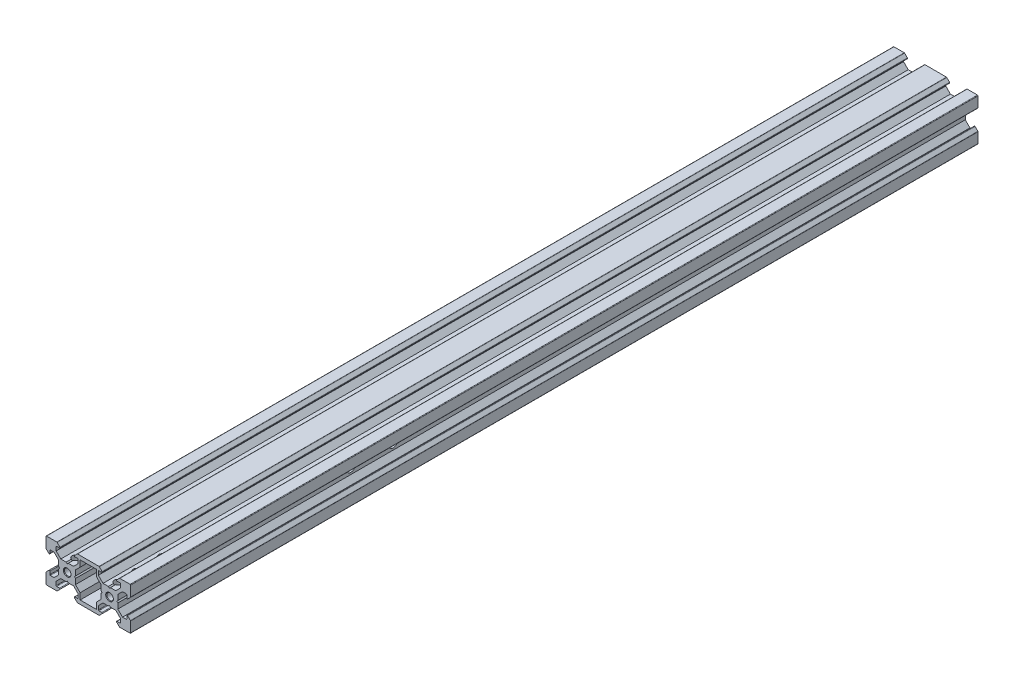
SolidWorks part; units mm, degrees
ref_plane "Alzado" through (0, 0, 0) normal (0, 0, 1) x (1, 0, 0)
ref_plane "Planta" through (0, 0, 0) normal (0, 1, 0) x (1, 0, 0)
ref_plane "Vista lateral" through (0, 0, 0) normal (1, 0, 0) x (0, 0, -1)
sketch "Croquis1" plane through (0, 0, 0) normal (0, 0, 1) x (1, 0, 0)
  line L0 (-10.0414, 10) -> (-10.0414, 8.2) construction
  line L1 (-13.8828, 8.2) -> (-6.2, 8.2)
  line L2 (-13.8828, -8.2) -> (-6.2, -8.2)
  line L4 (-4.8096, 9.9268) -> (-3.5096, 8.6268)
  line L5 (-3.6864, 8.2) -> (-5.0429, 8.2)
  line L6 (-5.2929, 7.95) -> (-5.2929, 6.2)
  line L13 (-14.8728, 8.2) -> (-16.6, 8.2)
  line L14 (-5.2929, 6.2) -> (-3.0929, 4)
  line L15 (-3.0929, 4) -> (-0.5828, 4)
  line L16 (-16.0828, 0.5) -> (-16.5828, 0)
  line L17 (-16.0828, 3.0101) -> (-16.0828, 0.5)
  line L18 (-13.8828, 5.2101) -> (-16.0828, 3.0101)
  line L19 (-13.8828, 8.2) -> (-13.8828, 5.2101)
  line L23 (-16.0828, -3.0101) -> (-16.0828, -0.5)
  line L24 (-16.0828, -0.5) -> (-16.5828, 0)
  line L25 (-13.8828, -5.2101) -> (-16.0828, -3.0101)
  line L26 (-13.8828, -8.2) -> (-13.8828, -5.2101)
  line L29 (-0.5828, 4) -> (-0.0828, 3.5)
  line L30 (-0.0828, 3.5) -> (0.4172, 4)
  line L31 (0.4172, 4) -> (2.9272, 4)
  line L32 (2.9272, 4) -> (5.1272, 6.2)
  line L33 (5.1272, 6.2) -> (5.1272, 7.95)
  line L34 (4.8772, 8.2) -> (3.5207, 8.2)
  line L35 (3.3439, 8.6268) -> (4.6439, 9.9268)
  line L36 (4.8207, 10) -> (9.6672, 10)
  line L37 (9.9172, 9.75) -> (9.9172, 4.9036)
  line L38 (9.8439, 4.7268) -> (8.5439, 3.4268)
  line L39 (8.1172, 3.6036) -> (8.1172, 4.9601)
  line L40 (7.8672, 5.2101) -> (6.1172, 5.2101)
  line L41 (6.1172, 5.2101) -> (3.9172, 3.0101)
  line L42 (3.9172, 3.0101) -> (3.9172, 0.5)
  line L43 (3.9172, 0.5) -> (3.4172, 0)
  line L44 (3.4172, 0) -> (3.9172, -0.5)
  line L45 (3.9172, -0.5) -> (3.9172, -3.0101)
  line L46 (3.9172, -3.0101) -> (6.1172, -5.2101)
  line L47 (6.1172, -5.2101) -> (7.8672, -5.2101)
  line L48 (8.1172, -4.9601) -> (8.1172, -3.6036)
  line L49 (8.5439, -3.4268) -> (9.8439, -4.7268)
  line L50 (9.9172, -4.9036) -> (9.9172, -9.75)
  line L51 (9.6672, -10) -> (4.8207, -10)
  line L52 (4.6439, -9.9268) -> (3.3439, -8.6268)
  line L53 (3.5207, -8.2) -> (4.8772, -8.2)
  line L54 (5.1272, -7.95) -> (5.1272, -6.2)
  line L55 (5.1272, -6.2) -> (2.9272, -4)
  line L56 (2.9272, -4) -> (0.4172, -4)
  line L57 (0.4172, -4) -> (-0.0828, -3.5)
  line L58 (-0.0828, -3.5) -> (-0.5828, -4)
  line L59 (-0.5828, -4) -> (-3.0929, -4)
  line L60 (-3.0929, -4) -> (-5.2929, -6.2)
  line L61 (-5.2929, -6.2) -> (-5.2929, -7.95)
  line L62 (-5.0429, -8.2) -> (-3.6864, -8.2)
  line L63 (-3.5096, -8.6268) -> (-4.8096, -9.9268)
  line L64 (-6.2, -8.2) -> (-6.2, -5.2101)
  line L65 (-6.2, -5.2101) -> (-4, -3.0101)
  line L66 (-4, -3.0101) -> (-4, -0.5)
  line L67 (-4, -0.5) -> (-3.5, 0)
  line L68 (-4, 0.5) -> (-3.5, 0)
  line L69 (-4, 3.0101) -> (-4, 0.5)
  line L70 (-6.2, 5.2101) -> (-4, 3.0101)
  line L71 (-6.2, 8.2) -> (-6.2, 5.2101)
  line L164 (-26.2, 5.2101) -> (-24, 3.0101)
  line L165 (-24, 3.0101) -> (-24, 0.5)
  line L166 (-24, 0.5) -> (-23.5, 0)
  line L167 (-23.5, 0) -> (-24, -0.5)
  line L168 (-24, -0.5) -> (-24, -3.0101)
  line L169 (-24, -3.0101) -> (-26.2, -5.2101)
  line L170 (-26.2, -5.2101) -> (-27.95, -5.2101)
  line L171 (-28.2, -4.9601) -> (-28.2, -3.6036)
  line L172 (-28.6268, -3.4268) -> (-29.9268, -4.7268)
  line L173 (-30, -4.9036) -> (-30, -9.75)
  line L174 (-29.75, -10) -> (-24.9036, -10)
  line L175 (-24.7268, -9.9268) -> (-23.4268, -8.6268)
  line L176 (-23.6036, -8.2) -> (-24.9601, -8.2)
  line L177 (-25.2101, -7.95) -> (-25.2101, -6.2)
  line L178 (-25.2101, -6.2) -> (-23.0101, -4)
  line L179 (-23.0101, -4) -> (-20.5, -4)
  line L180 (-20.5, -4) -> (-20, -3.5)
  line L181 (-20, -3.5) -> (-19.5, -4)
  line L182 (-19.5, -4) -> (-16.9899, -4)
  line L183 (-16.9899, -4) -> (-14.7899, -6.2)
  line L184 (-14.7899, -6.2) -> (-14.7899, -7.95)
  line L185 (-15.0399, -8.2) -> (-16.3964, -8.2)
  line L186 (-16.5732, -8.6268) -> (-15.2732, -9.9268)
  line L187 (-15.0964, -10) -> (-4.9864, -10)
  line L228 (-4.9864, 10) -> (-15.0964, 10)
  line L229 (-15.2732, 9.9268) -> (-16.5732, 8.6268)
  line L230 (-16.3964, 8.2) -> (-15.0399, 8.2)
  line L231 (-14.7899, 7.95) -> (-14.7899, 6.2)
  line L232 (-14.7899, 6.2) -> (-16.9899, 4)
  line L233 (-16.9899, 4) -> (-19.5, 4)
  line L234 (-19.5, 4) -> (-20, 3.5)
  line L235 (-20, 3.5) -> (-20.5, 4)
  line L236 (-20.5, 4) -> (-23.0101, 4)
  line L237 (-23.0101, 4) -> (-25.2101, 6.2)
  line L238 (-25.2101, 6.2) -> (-25.2101, 7.95)
  line L239 (-24.9601, 8.2) -> (-23.6036, 8.2)
  line L240 (-23.4268, 8.6268) -> (-24.7268, 9.9268)
  line L241 (-24.9036, 10) -> (-29.75, 10)
  line L242 (-30, 9.75) -> (-30, 4.9036)
  line L243 (-29.9268, 4.7268) -> (-28.6268, 3.4268)
  line L244 (-28.2, 3.6036) -> (-28.2, 4.9601)
  line L245 (-27.95, 5.2101) -> (-26.2, 5.2101)
  arc A0 (-3.5096, 8.6268) -> (-3.6864, 8.2) centre (-3.6864, 8.45) cw
  arc A1 (-15.0964, 10) -> (-15.2732, 9.9268) centre (-15.0964, 9.75) ccw
  arc A2 (-15.0399, 8.2) -> (-14.7899, 7.95) centre (-15.0399, 7.95) cw
  arc A4 (-16.5732, 8.6268) -> (-16.3964, 8.2) centre (-16.3964, 8.45) ccw
  arc A6 (-14.7899, -7.95) -> (-15.0399, -8.2) centre (-15.0399, -7.95) cw
  arc A7 (-16.3964, -8.2) -> (-16.5732, -8.6268) centre (-16.3964, -8.45) ccw
  arc A8 (-15.2732, -9.9268) -> (-15.0964, -10) centre (-15.0964, -9.75) ccw
  arc A9 (-24.9601, -8.2) -> (-25.2101, -7.95) centre (-24.9601, -7.95) cw
  arc A10 (-23.4268, -8.6268) -> (-23.6036, -8.2) centre (-23.6036, -8.45) ccw
  arc A11 (-24.9036, -10) -> (-24.7268, -9.9268) centre (-24.9036, -9.75) ccw
  arc A12 (-30, -9.75) -> (-29.75, -10) centre (-29.75, -9.75) ccw
  arc A13 (-29.9268, -4.7268) -> (-30, -4.9036) centre (-29.75, -4.9036) ccw
  arc A14 (-28.2, -3.6036) -> (-28.6268, -3.4268) centre (-28.45, -3.6036) ccw
  arc A15 (-27.95, -5.2101) -> (-28.2, -4.9601) centre (-27.95, -4.9601) cw
  arc A16 (-24.7268, 9.9268) -> (-24.9036, 10) centre (-24.9036, 9.75) ccw
  arc A17 (-23.6036, 8.2) -> (-23.4268, 8.6268) centre (-23.6036, 8.45) ccw
  arc A18 (-25.2101, 7.95) -> (-24.9601, 8.2) centre (-24.9601, 7.95) cw
  arc A19 (-28.2, 4.9601) -> (-27.95, 5.2101) centre (-27.95, 4.9601) cw
  arc A20 (-28.6268, 3.4268) -> (-28.2, 3.6036) centre (-28.45, 3.6036) ccw
  arc A21 (-30, 4.9036) -> (-29.9268, 4.7268) centre (-29.75, 4.9036) ccw
  arc A22 (-29.75, 10) -> (-30, 9.75) centre (-29.75, 9.75) ccw
  arc A23 (-5.0429, 8.2) -> (-5.2929, 7.95) centre (-5.0429, 7.95) ccw
  arc A24 (5.1272, 7.95) -> (4.8772, 8.2) centre (4.8772, 7.95) ccw
  arc A25 (3.5207, 8.2) -> (3.3439, 8.6268) centre (3.5207, 8.45) cw
  arc A26 (4.6439, 9.9268) -> (4.8207, 10) centre (4.8207, 9.75) cw
  arc A27 (9.6672, 10) -> (9.9172, 9.75) centre (9.6672, 9.75) cw
  arc A28 (9.9172, 4.9036) -> (9.8439, 4.7268) centre (9.6672, 4.9036) cw
  arc A29 (8.5439, 3.4268) -> (8.1172, 3.6036) centre (8.3672, 3.6036) cw
  arc A30 (8.1172, 4.9601) -> (7.8672, 5.2101) centre (7.8672, 4.9601) ccw
  arc A31 (7.8672, -5.2101) -> (8.1172, -4.9601) centre (7.8672, -4.9601) ccw
  arc A32 (8.1172, -3.6036) -> (8.5439, -3.4268) centre (8.3672, -3.6036) cw
  arc A33 (9.8439, -4.7268) -> (9.9172, -4.9036) centre (9.6672, -4.9036) cw
  arc A34 (9.9172, -9.75) -> (9.6672, -10) centre (9.6672, -9.75) cw
  arc A35 (4.8207, -10) -> (4.6439, -9.9268) centre (4.8207, -9.75) cw
  arc A36 (3.3439, -8.6268) -> (3.5207, -8.2) centre (3.5207, -8.45) cw
  arc A37 (4.8772, -8.2) -> (5.1272, -7.95) centre (4.8772, -7.95) ccw
  arc A38 (-5.2929, -7.95) -> (-5.0429, -8.2) centre (-5.0429, -7.95) ccw
  arc A39 (-3.6864, -8.2) -> (-3.5096, -8.6268) centre (-3.6864, -8.45) cw
  arc A40 (-4.8096, -9.9268) -> (-4.9864, -10) centre (-4.9864, -9.75) cw
  arc A41 (-4.9864, 10) -> (-4.8096, 9.9268) centre (-4.9864, 9.75) cw
  point P47 (-10.0414, -8.2)
  point P134 (-10.0414, 8.2)
  dimension "D1" = 0.25
extrude "Saliente-Extruir1" add sketch "Croquis1" along normal blind 200 and the other way blind 200 contours A41 L228 L1 L71 L70 L69 L68 L67 L66 L65 L64 L2 L26 L25 L23 L24 L16 L17 L18 L19 A1 L229 A4 L13 A2 L231 L232 L233 L234 L235 L236 L237 L238 A18 L239 A17 L240 A16 L241 A22 L242 A21 L243 A20 L244 region at (-4.4753, 8.9611, 0)
sketch "Croquis4" plane through (0, 0, 200) normal (0, 0, 1) x (1, 0, 0)
  line L0 (-24.6708, 0) -> (6.8007, 0) construction
  line L1 (-20, 3.5) -> (-20, 0) construction
  circle A0 centre (-20, 0) radius 1.5693
  circle A1 centre (0, 0) radius 1.5693
extrude "Cortar-Extruir1" cut sketch "Croquis4" against normal through all
chamfer "Chaflán1" distance 0.25 angle 45 4 edges at (-18.4307, 0, -200) (1.5693, 0, -200) (1.5693, 0, 200) (-18.4307, 0, 200)
sketch "Croquis5" plane through (0, 10, 0) normal (0, 1, 0) x (1, 0, 0)
  line L0 (-20, 200) -> (-20, -200) construction
  line L1 (-0.0828, 200) -> (-0.0828, -200) construction
  line L2 (-24.9036, -200) -> (-29.75, -200) construction
  line L3 (4.8207, -200) -> (9.6672, -200) construction
  circle A0 centre (-20, -196) radius 1.65
  circle A1 centre (-0.0828, -196) radius 1.65
  circle A2 centre (-0.0828, -187) radius 1.65
  circle A3 centre (-0.0828, -175) radius 1.65
  point P0 (-20, -196)
  point P1 (-0.0828, -196)
  point P4 (-0.0828, -187)
  point P7 (-0.0828, -175)
  dimension "D5" = 3.3
  dimension "D6" = 3.3
  dimension "D7" = 3.3
  dimension "D8" = 3.3
  dimension "D1" = 4
  dimension "D2" = 4
  dimension "D3" = 9
  dimension "D4" = 12
extrude "Cortar-Extruir2" cut sketch "Croquis5" against normal through all
sketch "Croquis6" plane through (9.9172, 0, 0) normal (1, 0, 0) x (0, 0, -1)
  line L0 (200, 0) -> (-200, 0) construction
  line L2 (-200, -4.9036) -> (-200, -9.75) construction
  circle A0 centre (-90, 0) radius 2.1
  circle A1 centre (-70, 0) radius 2.1
  dimension "D1" = 4.2
  dimension "D2" = 110
  dimension "D3" = 20
extrude "Cortar-Extruir3" cut sketch "Croquis6" against normal through all
ref_plane "Plano1" through (0, 10, 0) normal (0, 1, 0) x (1, 0, 0)
sketch "Croquis7" plane through (0, 10, 0) normal (0, 1, 0) x (1, 0, 0)
  line L0 (-0.0828, -208.2854) -> (-0.0828, 204.3207) construction
  line L1 (-20, 203.8797) -> (-20, -203.8298) construction
ref_plane "Plano2" through (0, -10, 0) normal (0, 1, 0) x (1, 0, 0)
sketch "Croquis9" plane through (0, -10, 0) normal (0, 1, 0) x (1, 0, 0)
  line L0 (-0.0828, -208.2854) -> (-0.0828, 204.3207) construction
  line L1 (-20, 203.8797) -> (-20, -203.8298) construction
ref_plane "Plano3" through (0, -8.6268, 0) normal (0, -1, 0) x (-1, 0, 0)
ref_plane "Plano4" through (0, -8.6268, 0) normal (0, 1, 0) x (1, 0, 0)
ref_plane "Plano5" through (0, 8.6268, 0) normal (0, 1, 0) x (1, 0, 0)
ref_plane "Plano6" through (0, 8.6268, 0) normal (0, 1, 0) x (1, 0, 0)
